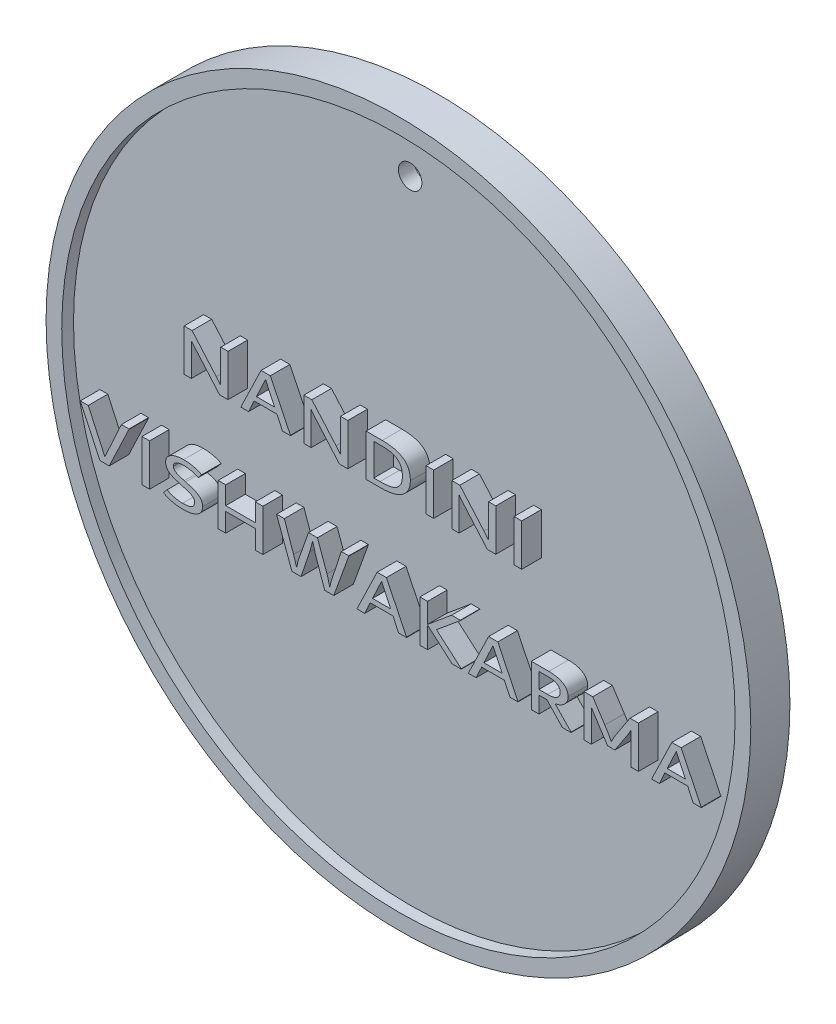
SolidWorks part; units mm, degrees
ref_plane "Front Plane" through (0, 0, 0) normal (0, 0, 1) x (1, 0, 0)
ref_plane "Top Plane" through (0, 0, 0) normal (0, 1, 0) x (1, 0, 0)
ref_plane "Right Plane" through (0, 0, 0) normal (1, 0, 0) x (0, 0, -1)
sketch "Sketch1" plane through (0, 0, 0) normal (0, 0, 1) x (1, 0, 0)
  circle A0 centre (0, 0) radius 45
extrude "Boss-Extrude1" add sketch "Sketch1" along normal blind 5
sketch "Sketch2" plane through (0, 0, 5) normal (0, 0, 1) x (1, 0, 0)
  circle A3 centre (0, 0) radius 43
  circle A4 centre (0, 0) radius 43
  dimension "D1" = 2
extrude "Cut-Extrude1" cut sketch "Sketch2" against normal blind 1.5
sketch "Sketch3" plane through (0, 0, 0) normal (0, 0, -1) x (-1, 0, 0)
  circle A2 centre (0, 0) radius 43
  circle A3 centre (0, 0) radius 43
  dimension "D1" = 2
extrude "Cut-Extrude2" cut sketch "Sketch3" against normal blind 1.5
sketch "Sketch4" plane through (0, 0, 1.5) normal (0, 0, -1) x (-1, 0, 0)
  circle A0 centre (0, 37.6269) radius 1.5
  dimension "D1" = 3
extrude "Cut-Extrude3" cut sketch "Sketch4" against normal blind 31.5 contours A0
sketch "Sketch5" plane through (0, 0, 3.5) normal (0, 0, 1) x (1, 0, 0)
  text T0 "    NANDINI\r\nVISHWAKARMA" font "Dubai" height in points 20
extrude "Boss-Extrude2" add sketch "Sketch5" along normal blind 2.5
sketch "Sketch6" plane through (0, 0, 1.5) normal (0, 0, -1) x (-1, 0, 0)
  line L0 (-35.184, -24.7201) -> (-24.6621, -3.5673)
  line L1 (-22.0004, -3.5204) -> (-12.3828, -21.2567)
  line L2 (-12.3828, -21.2567) -> (-10.5229, -17.5176)
  line L3 (-7.8613, -17.4707) -> (-5.8083, -21.2567)
  line L4 (-5.8083, -21.2567) -> (2.9909, -3.5673)
  line L5 (5.6525, -3.5204) -> (13.5556, -18.0949)
  line L6 (13.5556, -18.0949) -> (19.9245, -8.55)
  line L7 (22.4525, -8.6009) -> (33.5912, -26.8446)
  circle A0 centre (0, 0) radius 43 construction
  circle A1 centre (0, 0) radius 43 construction
  arc A2 (22.4525, -8.6009) -> (19.9245, -8.55) centre (21.1723, -9.3825) ccw
  arc A3 (5.6525, -3.5204) -> (2.9909, -3.5673) centre (4.3339, -4.2354) ccw
  arc A4 (-7.8613, -17.4707) -> (-10.5229, -17.5176) centre (-9.1799, -18.1857) ccw
  arc A5 (-22.0004, -3.5204) -> (-24.6621, -3.5673) centre (-23.319, -4.2354) ccw
  arc A6 (-35.184, -24.7201) -> (33.5912, -26.8446) centre (0, 0) ccw
  dimension "D1" = 1.5
extrude "Boss-Extrude3" add sketch "Sketch6" along normal blind 2.5
sketch "Sketch7" plane through (0, 0, 1.5) normal (0, 0, -1) x (-1, 0, 0)
  circle A0 centre (19.7261, 18.1115) radius 8.0027
  arc A2 (13.9716, 23.6729) -> (20.9107, 10.1969) centre (17.4411, 16.9349) cw
extrude "Boss-Extrude4" add sketch "Sketch7" along normal blind 2.5 contours A0 A2 region at (-25.6299, 13.0256, 1.5)
sketch "Sketch8" plane through (0, 0, 1.5) normal (0, 0, -1) x (-1, 0, 0)
  line L1 (-23.938, 22.0426) -> (-24.3968, 23.3989)
  line L2 (-24.3968, 23.3989) -> (-25.8008, 23.6797)
  line L3 (-25.8008, 23.6797) -> (-26.746, 22.6042)
  line L4 (-26.746, 22.6042) -> (-26.2872, 21.248)
  line L5 (-26.2872, 21.248) -> (-24.8832, 20.9672)
  line L6 (-24.8832, 20.9672) -> (-23.938, 22.0426)
  line L7 (-12.2849, 31.7302) -> (-11.944, 33.3861)
  line L8 (-11.944, 33.3861) -> (-13.2076, 34.5093)
  line L9 (-13.2076, 34.5093) -> (-14.8121, 33.9766)
  line L10 (-14.8121, 33.9766) -> (-15.153, 32.3207)
  line L11 (-15.153, 32.3207) -> (-13.8894, 31.1975)
  line L12 (-13.8894, 31.1975) -> (-12.2849, 31.7302)
  line L13 (-12.2849, 21.5049) -> (-12.6215, 23.1633)
  line L14 (-12.6215, 23.1633) -> (-14.226, 23.7011)
  line L15 (-14.226, 23.7011) -> (-15.4939, 22.5804)
  line L16 (-15.4939, 22.5804) -> (-15.1574, 20.922)
  line L17 (-15.1574, 20.922) -> (-13.5529, 20.3842)
  line L18 (-13.5529, 20.3842) -> (-12.2849, 21.5049)
  line L19 (5.2567, 29.8448) -> (3.9702, 31.0371)
  line L20 (3.9702, 31.0371) -> (2.2943, 30.519)
  line L21 (2.2943, 30.519) -> (1.9051, 28.8087)
  line L22 (1.9051, 28.8087) -> (3.1916, 27.6164)
  line L23 (3.1916, 27.6164) -> (4.8674, 28.1345)
  line L24 (4.8674, 28.1345) -> (5.2567, 29.8448)
  line L25 (-1.3338, 19.3751) -> (-0.881, 20.6092)
  line L26 (-0.881, 20.6092) -> (-1.7234, 21.6183)
  line L27 (-1.7234, 21.6183) -> (-3.0186, 21.3934)
  line L28 (-3.0186, 21.3934) -> (-3.4713, 20.1593)
  line L29 (-3.4713, 20.1593) -> (-2.6289, 19.1501)
  line L30 (-2.6289, 19.1501) -> (-1.3338, 19.3751)
  line L31 (-10.3249, 9.1259) -> (-11.3049, 10.8234)
  line L32 (-11.3049, 10.8234) -> (-13.2649, 10.8234)
  line L33 (-13.2649, 10.8234) -> (-14.245, 9.1259)
  line L34 (-14.245, 9.1259) -> (-13.2649, 7.4285)
  line L35 (-13.2649, 7.4285) -> (-11.3049, 7.4285)
  line L36 (-11.3049, 7.4285) -> (-10.3249, 9.1259)
  line L37 (-24.8832, 13.7591) -> (-25.1264, 13.6187)
  line L38 (-25.1264, 13.6187) -> (-25.1264, 13.3379)
  line L39 (-25.1264, 13.3379) -> (-24.8832, 13.1975)
  line L40 (-24.8832, 13.1975) -> (-24.64, 13.3379)
  line L41 (-24.64, 13.3379) -> (-24.64, 13.6187)
  line L42 (-24.64, 13.6187) -> (-24.8832, 13.7591)
  line L43 (-29.9752, 8.2772) -> (-30.4666, 9.1283)
  line L44 (-30.4666, 9.1283) -> (-31.4494, 9.1283)
  line L45 (-31.4494, 9.1283) -> (-31.9408, 8.2772)
  line L46 (-31.9408, 8.2772) -> (-31.4494, 7.4261)
  line L47 (-31.4494, 7.4261) -> (-30.4666, 7.4261)
  line L48 (-30.4666, 7.4261) -> (-29.9752, 8.2772)
  line L49 (32.5024, 19.9921) -> (32.6156, 21.0302)
  line L50 (32.6156, 21.0302) -> (31.7732, 21.6472)
  line L51 (31.7732, 21.6472) -> (30.8176, 21.2262)
  line L52 (30.8176, 21.2262) -> (30.7044, 20.1882)
  line L53 (30.7044, 20.1882) -> (31.5468, 19.5711)
  line L54 (31.5468, 19.5711) -> (32.5024, 19.9921)
  line L55 (32.0246, 9.1259) -> (32.5207, 9.9641)
  line L56 (32.5207, 9.9641) -> (32.0429, 10.8128)
  line L57 (32.0429, 10.8128) -> (31.069, 10.8234)
  line L58 (31.069, 10.8234) -> (30.5729, 9.9852)
  line L59 (30.5729, 9.9852) -> (31.0507, 9.1365)
  line L60 (31.0507, 9.1365) -> (32.0246, 9.1259)
  line L61 (37.3964, 13.2677) -> (37.2695, 13.9087)
  line L62 (37.2695, 13.9087) -> (36.6508, 14.1193)
  line L63 (36.6508, 14.1193) -> (36.1591, 13.6889)
  line L64 (36.1591, 13.6889) -> (36.2861, 13.0479)
  line L65 (36.2861, 13.0479) -> (36.9047, 12.8373)
  line L66 (36.9047, 12.8373) -> (37.3964, 13.2677)
  line L67 (11.0213, 13.0479) -> (11.1553, 14.0979)
  line L68 (11.1553, 14.0979) -> (10.3129, 14.739)
  line L69 (10.3129, 14.739) -> (9.3365, 14.3299)
  line L70 (9.3365, 14.3299) -> (9.2026, 13.2799)
  line L71 (9.2026, 13.2799) -> (10.045, 12.6389)
  line L72 (10.045, 12.6389) -> (11.0213, 13.0479)
  line L73 (3.1916, 8.2772) -> (3.9266, 8.7016)
  line L74 (3.9266, 8.7016) -> (3.9266, 9.5503)
  line L75 (3.9266, 9.5503) -> (3.1916, 9.9747)
  line L76 (3.1916, 9.9747) -> (2.4566, 9.5503)
  line L77 (2.4566, 9.5503) -> (2.4566, 8.7016)
  line L78 (2.4566, 8.7016) -> (3.1916, 8.2772)
  line L79 (-1.3338, 3.5511) -> (-1.9814, 4.6727)
  line L80 (-1.9814, 4.6727) -> (-3.2765, 4.6727)
  line L81 (-3.2765, 4.6727) -> (-3.9241, 3.5511)
  line L82 (-3.9241, 3.5511) -> (-3.2765, 2.4294)
  line L83 (-3.2765, 2.4294) -> (-1.9814, 2.4294)
  line L84 (-1.9814, 2.4294) -> (-1.3338, 3.5511)
  circle A0 centre (-25.342, 22.3234) radius 1.24 construction
  circle A1 centre (-13.5485, 32.8534) radius 1.4641 construction
  circle A2 centre (-13.8894, 22.0426) radius 1.4655 construction
  circle A3 centre (3.5809, 29.3268) radius 1.5191 construction
  circle A4 centre (-2.1762, 20.3842) radius 1.1384 construction
  circle A5 centre (-12.2849, 9.1259) radius 1.6975 construction
  circle A6 centre (-24.8832, 13.4783) radius 0.2432 construction
  circle A7 centre (-30.958, 8.2772) radius 0.8511 construction
  circle A8 centre (31.66, 20.6092) radius 0.9043 construction
  circle A9 centre (31.5468, 9.9747) radius 0.8435 construction
  circle A10 centre (36.7778, 13.4783) radius 0.5659 construction
  circle A11 centre (10.1789, 13.6889) radius 0.9167 construction
  circle A12 centre (3.1916, 9.1259) radius 0.735 construction
  circle A13 centre (-2.6289, 3.5511) radius 1.1216 construction
extrude "Boss-Extrude5" add sketch "Sketch8" along normal blind 2.5
